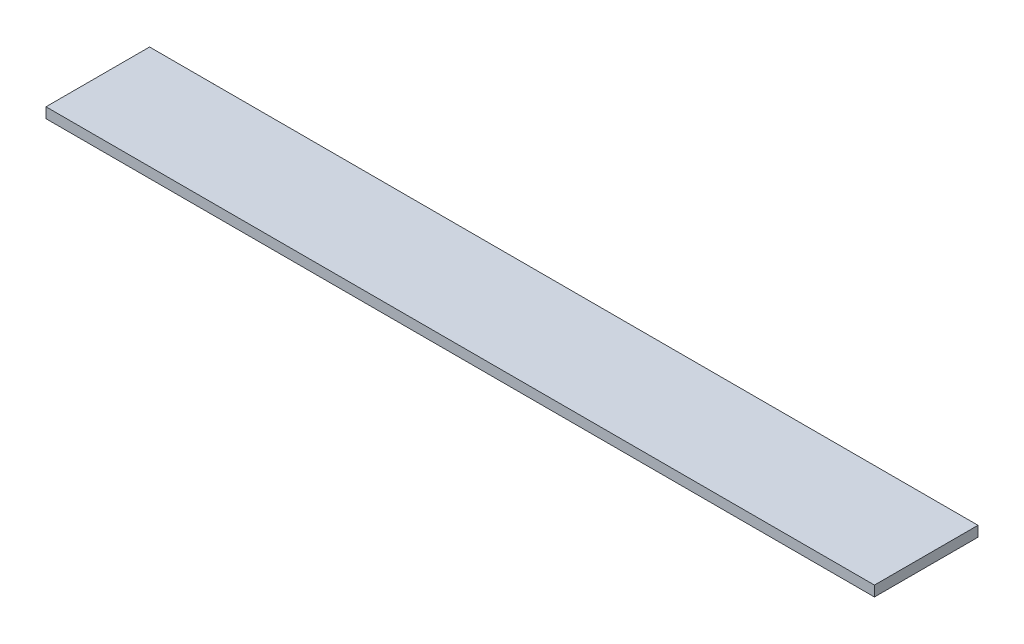
SolidWorks part; units mm, degrees
ref_plane "Front Plane" through (0, 0, 0) normal (0, 0, 1) x (1, 0, 0)
ref_plane "Top Plane" through (0, 0, 0) normal (0, 1, 0) x (1, 0, 0)
ref_plane "Right Plane" through (0, 0, 0) normal (1, 0, 0) x (0, 0, -1)
sketch "Sketch1" plane through (0, 0, 0) normal (0, 1, 0) x (1, 0, 0)
  line L1 (-400, 50) -> (400, 50)
  line L2 (-400, 50) -> (-400, -50)
  line L3 (-400, -50) -> (400, -50)
  line L4 (400, 50) -> (400, -50)
  line L5 (-400, 50) -> (400, -50) construction
  line L6 (-400, -50) -> (400, 50) construction
  point P0 (0, 0)
  dimension "D1" = 100
  dimension "D2" = 800
extrude "Boss-Extrude1" add sketch "Sketch1" against normal blind 10
